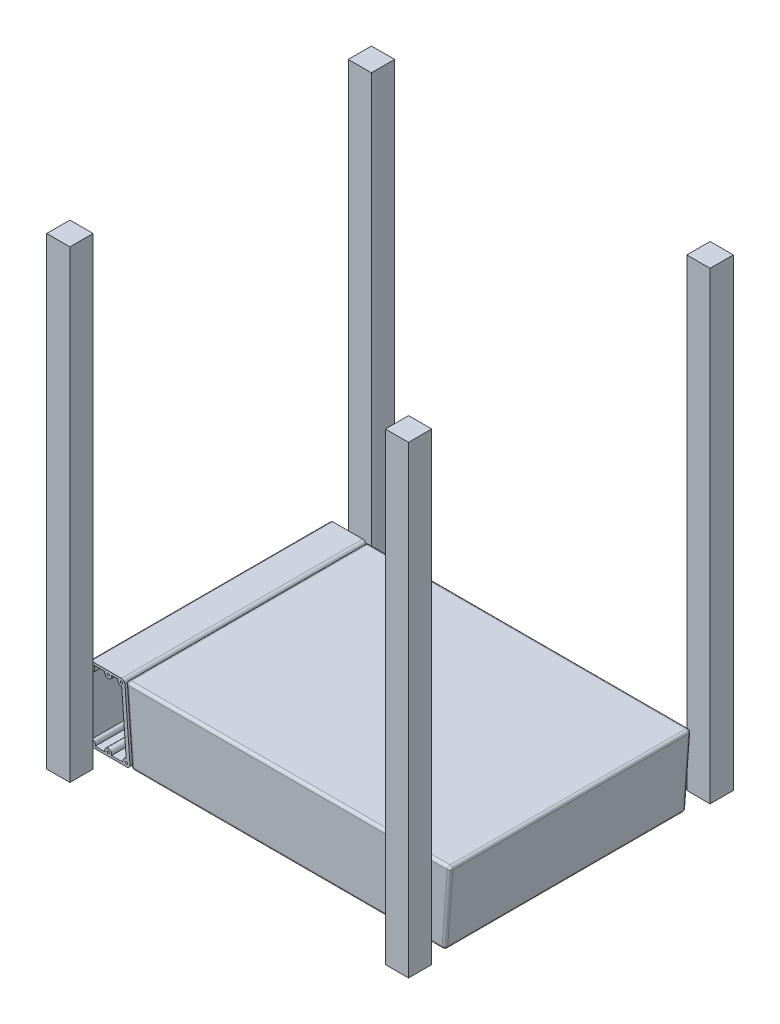
SolidWorks part; units mm, degrees
note: The reader was unsure of these and kept them because the rebuilt part matched: shared geometry of "스케치1<9>", "스케치32<7>".
ref_plane "정면" through (0, 0, 0) normal (0, 0, 1) x (1, 0, 0)
ref_plane "윗면" through (0, 0, 0) normal (0, 1, 0) x (1, 0, 0)
ref_plane "우측면" through (0, 0, 0) normal (1, 0, 0) x (0, 0, -1)
sketch "스케치1" plane through (0, 0, 0) normal (0, 1, 0) x (1, 0, 0)
  line L0 (-219.6919, 0) -> (219.6919, 0) construction
  line L1 (0, 196.2965) -> (0, -196.2965) construction
  line L2 (-170, -223.845) -> (-170, 264.5659) construction
  line L3 (-195, 150) -> (195, 150)
  line L4 (-195, 150) -> (-195, -150)
  line L5 (-195, -150) -> (195, -150)
  line L6 (195, 150) -> (195, -150)
  line L7 (-195, 150) -> (195, -150) construction
  line L8 (-195, -150) -> (195, 150) construction
  line L9 (195, 130) -> (-155, 130)
  line L10 (195, 130) -> (195, -130)
  line L11 (195, -130) -> (-155, -130)
  line L12 (-155, 130) -> (-155, -130)
  line L13 (-149, 130) -> (189, 130)
  line L14 (-149, 130) -> (-149, -130)
  line L15 (-149, -130) -> (189, -130)
  line L16 (189, 130) -> (189, -130)
  line L17 (-195, -150) -> (-170, -150)
  line L18 (-195, -150) -> (-195, -175)
  line L19 (-195, -175) -> (-170, -175)
  line L20 (-170, -150) -> (-170, -175)
  line L21 (195, -150) -> (170, -150)
  line L22 (195, -150) -> (195, -175)
  line L23 (195, -175) -> (170, -175)
  line L24 (170, -150) -> (170, -175)
  line L25 (-195, 150) -> (-170, 150)
  line L26 (-195, 150) -> (-195, 175)
  line L27 (-195, 175) -> (-170, 175)
  line L28 (-170, 150) -> (-170, 175)
  line L29 (195, 150) -> (170, 150)
  line L30 (195, 150) -> (195, 175)
  line L31 (195, 175) -> (170, 175)
  line L32 (170, 150) -> (170, 175)
  line L33 (-195, 130) -> (-155, 130)
  line L34 (-195, 130) -> (-195, -130)
  line L35 (-195, -130) -> (-155, -130)
  line L36 (-155, 130) -> (-155, -130)
  line L37 (-195, 130) -> (-155, 130)
  line L38 (-195, 130) -> (-195, -130)
  line L39 (-195, -130) -> (-155, -130)
  line L40 (-155, 130) -> (-155, -130)
  point P5 (0, 0)
  point P6 (0, 0)
  point P7 (0, 0)
  point P21 (-155, 0)
  dimension "D1" = 390
  dimension "D2" = 300
  dimension "D3" = 260
  dimension "D4" = 350
  dimension "D5" = 6
  dimension "D6" = 338
  dimension "D7" = 25
  dimension "D8" = 25
  dimension "D9" = 25
  dimension "D10" = 25
  dimension "D11" = 25
  dimension "D12" = 25
  dimension "D13" = 25
  dimension "D14" = 25
extrude "보스-돌출5" add sketch "스케치1" along normal blind 80 contours L12 L11 L10 L9
sketch "스케치5" plane through (0, 0, 130) normal (0, 0, 1) x (1, 0, 0)
  line L0 (-155, 80) -> (-149, 0)
  line L1 (-149, 0) -> (-155, 0)
  line L2 (-155, 0) -> (-155, 80)
extrude "컷-돌출1" cut sketch "스케치5" against normal blind 262
sketch "스케치6" plane through (0, 0, 130) normal (0, 0, 1) x (1, 0, 0)
  line L0 (195, 0) -> (189, 0)
  line L1 (189, 0) -> (195, 80)
  line L2 (195, 80) -> (195, 0)
extrude "컷-돌출2" cut sketch "스케치6" against normal blind 262
fillet "필렛2" radius 3 12 edges at (192, 40, -130) (-152, 40, -130) (-149, 0, 0) (189, 0, 0) (20, 0, -130) (195, 80, 0) (-155, 80, 0) (20, 80, -130) (20, 0, 130) (-152, 40, 130) (20, 80, 130) (192, 40, 130)
extrude "보스-돌출6" add sketch "스케치1<9>" along normal blind 500 separate body contours L20 L5 L18 L19 | L5 L24 L23 L22 | L32 L3 L30 L31 | L26 L27 L28 L25
sketch "스케치1<9>" plane through (0, 0, 0) normal (0, 1, 0) x (1, 0, 0) same geometry as "스케치1"
sketch "스케치7" plane through (0, 0, -150) normal (0, 0, 1) x (1, 0, 0)
  line L0 (-195, 0) -> (195, 0) construction
  line L1 (-188.0182, 92.3) -> (-176.4182, 92.3)
  line L2 (-188.0182, 92.3) -> (-188.0182, 89.7)
  line L3 (-188.0182, 89.7) -> (-176.4182, 89.7)
  line L4 (-176.4182, 92.3) -> (-176.4182, 89.7)
  dimension "D1" = 11.6
  dimension "D2" = 2.6
  dimension "D3" = 89.7
sketch "스케치8" plane through (0, 0, -150) normal (0, 0, 1) x (1, 0, 0)
  line L0 (-188.0182, 92.3) -> (-176.4182, 92.3) construction
  line L1 (-188.0182, 116.8) -> (-176.4182, 116.8)
  line L2 (-188.0182, 116.8) -> (-188.0182, 114.2)
  line L3 (-188.0182, 114.2) -> (-176.4182, 114.2)
  line L4 (-176.4182, 116.8) -> (-176.4182, 114.2)
  line L6 (-176.4182, 92.3) -> (-176.4182, 89.7) construction
  dimension "D1" = 2.6
  dimension "D2" = 11.6
  dimension "D3" = 21.9
ref_plane "평면9" through (-149.1638, -11.1873, 0) normal (-0.9972, -0.0748, 0) x (0, 0, 1)
ref_plane "평면10" through (0, 0, 130) normal (0, 0, 1) x (1, 0, 0)
sketch "스케치32" plane through (0, 0, 130) normal (0, 0, 1) x (1, 0, 0)
  line L0 (-195, 93.5657) -> (-195, -43.1287) construction
  line L1 (-195, 0) -> (-170, 0) construction
  line L2 (-170, -62.39) -> (-170, 85.6149) construction
  line L3 (-222.7165, 80) -> (-134.2239, 80) construction
  line L4 (-152.2163, 29.5127) -> (-146.1113, -51.8873) construction
  line L5 (-191.25, 3.75) -> (-191.25, 71.5)
  line L6 (-192.5, 3.75) -> (-195, 3.75)
  line L7 (-195, 0) -> (195, 0) construction
  line L9 (-154.0446, 3.75) -> (-150.3051, 4.0305)
  line L10 (-191.25, 2.5) -> (-154.0446, 2.5)
  line L11 (-191.25, 2.5) -> (-191.25, 0)
  line L12 (-191.25, 0) -> (-154.0446, 0)
  line L13 (-154.0446, 2.5) -> (-154.0446, 0)
  line L14 (-154.0446, 3.75) -> (-159.4821, 76.25)
  line L15 (-159.4821, 76.25) -> (-155.7426, 76.5305)
  line L16 (-150.3051, 4.0305) -> (-155.7426, 76.5305)
  line L18 (-195, 3.75) -> (-195, 80)
  line L23 (-191.25, 71.5) -> (-188.75, 71.5)
  line L24 (-188.75, 71.5) -> (-188.75, 77)
  line L25 (-188.75, 77) -> (-191, 77)
  line L26 (-191, 77) -> (-191, 74.5)
  line L27 (-191, 74.5) -> (-195, 74.5)
  line L32 (-191.25, 3.75) -> (-192.5, 3.75)
  line L33 (-191.438, 91.6256) -> (-201.7492, 91.6256) construction
  line L34 (-159.4821, 77.5) -> (-190.5499, 77.5)
  line L35 (-159.4821, 77.5) -> (-159.4821, 80)
  line L38 (-191.5306, 80) -> (-192, 80)
  line L41 (-194, 78) -> (-194, 77)
  line L42 (-194, 77) -> (-194, 75)
  line L43 (-194, 75) -> (-191.5, 75)
  line L44 (-191.5, 77.5) -> (-190.5499, 77.5)
  line L45 (-191.5, 77.5) -> (-191.5, 75)
  line L46 (-173.75, 80) -> (-191.5306, 80)
  line L47 (-173.75, 80) -> (-159.4821, 80)
  line L49 (-191.25, 80) -> (-195, 80)
  line L50 (-191.25, 80) -> (-191.25, 108.4206)
  line L51 (-191.25, 108.4206) -> (-195, 108.4206)
  line L52 (-195, 80) -> (-195, 108.4206)
  circle A0 centre (-191.25, 3.75) radius 3.75
  circle A1 centre (-191.25, 3.75) radius 1.25
  circle A2 centre (-154.0446, 3.75) radius 3.75
  circle A3 centre (-154.0446, 3.75) radius 1.25
  circle A4 centre (-159.4821, 76.25) radius 3.75
  circle A5 centre (-159.4821, 76.25) radius 1.25
  circle A6 centre (-173.75, 3.75) radius 3.75
  circle A7 centre (-173.75, 3.75) radius 1.25
  circle A8 centre (-173.75, 76.25) radius 3.75
  circle A9 centre (-173.75, 76.25) radius 1.25
  arc A10 (-192, 80) -> (-194, 78) centre (-192, 78) ccw
  point P55 (-194, 80)
  point P59 (-194, 75)
  dimension "D2" = 2.5
  dimension "D3" = 7.5
  dimension "D4" = 7.5
  dimension "D5" = 2.5
  dimension "D6" = 2.5
  dimension "D7" = 7.5
  dimension "D8" = 7.5
  dimension "D9" = 2.5
  dimension "D10" = 25
  dimension "D11" = 7.5
  dimension "D12" = 2.5
  dimension "D21" = 2
  dimension "D1" = 15
  dimension "D13" = 4
  dimension "D14" = 2.5
  dimension "D15" = 5.5
  dimension "D16" = 5.5
  dimension "D17" = 2.5
  dimension "D18" = 2.5
  dimension "D19" = 5
  dimension "D20" = 1
extrude "보스-돌출17" add sketch "스케치32" against normal blind 260 separate body
extrude "보스-돌출18" add sketch "스케치32<7>" against normal blind 260 contours A5 L15 A4 L35 | L35 A4 L34 | A8 L34 A4 L47 | L34 A8 | L34 A9 A8 | L38 A10 L41 L42 L43 L45 L44 L34 A8 L46
sketch "스케치32<7>" plane through (0, 0, 130) normal (0, 0, 1) x (1, 0, 0) same geometry as "스케치32"
